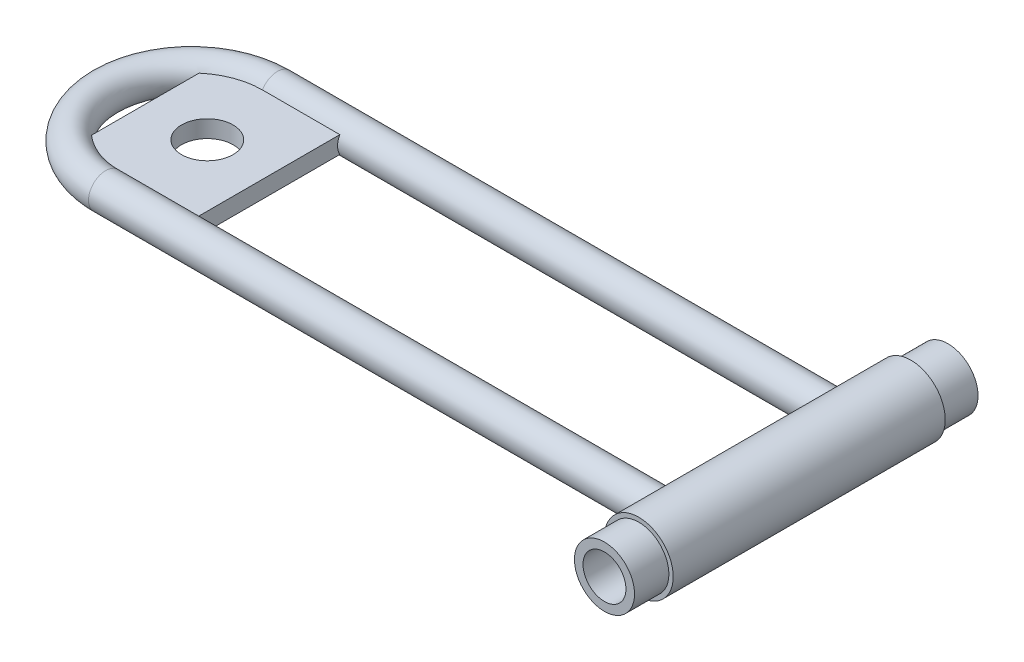
SolidWorks part; units mm, degrees
ref_plane "Front Plane" through (0, 0, 0) normal (0, 0, 1) x (1, 0, 0)
ref_plane "Top Plane" through (0, 0, 0) normal (0, 1, 0) x (1, 0, 0)
ref_plane "Right Plane" through (0, 0, 0) normal (1, 0, 0) x (0, 0, -1)
sketch "Sketch1" plane through (0, 0, 0) normal (0, 0, 1) x (1, 0, 0)
  circle A0 centre (0, 0) radius 6.35
  circle A1 centre (0, 0) radius 3.175
  dimension "D1" = 12.7
  dimension "D2" = 3.175
extrude "Boss-Extrude1" add sketch "Sketch1" along normal blind 62.992
ref_plane "Plane1" through (-3.81, 0, 0) normal (-1, 0, 0) x (0, 0, 1)
sketch "Sketch3" plane through (-3.81, 0, 0) normal (-1, 0, 0) x (0, 0, 1)
  line L0 (0, 0) -> (62.992, 0)
  line L1 (62.992, -6.35) -> (62.992, 6.35) construction
  circle A0 centre (-15.748, 0) radius 3.175
  circle A1 centre (47.244, 0) radius 3.175
  dimension "D3" = 6.35
  dimension "D4" = 6.35
  dimension "D1" = 15.748
  dimension "D2" = 15.748
sketch "Sketch4" plane through (0, 0, 0) normal (0, 1, 0) x (1, 0, 0)
  line L0 (-3.81, -15.6639) -> (-107.95, -15.6639)
  line L1 (-3.81, 0) -> (-3.81, -62.992) construction
  line L2 (-3.81, -47.0944) -> (-107.95, -47.0944)
  line L3 (-6.35, 0) -> (-6.35, -62.992) construction
  arc A0 (-107.95, -15.6639) -> (-107.95, -47.0944) centre (-107.95, -31.3792) ccw
  dimension "D1" = 101.6
  dimension "D2" = 15.7152
  dimension "D3" = 31.3792
sweep "Sweep1" add profiles "Sketch3" path "Sketch4"
ref_plane "Plane2" through (0, 0, 15.24) normal (0, 0, 1) x (1, 0, 0)
sketch "Sketch6" plane through (0, 0, 15.24) normal (0, 0, 1) x (1, 0, 0)
  line L0 (-116.5013, 0) -> (-93.6413, 0)
  line L3 (-93.6413, 0) -> (-116.5013, 0)
  line L4 (-93.6413, 0) -> (-93.6413, -1.5875)
  line L5 (-93.6413, -1.5875) -> (-116.5013, -1.5875)
  line L6 (-116.5013, 0) -> (-116.5013, -1.5875)
  line L7 (-93.6413, 0) -> (-116.5013, 0)
  line L8 (-93.6413, 0) -> (-93.6413, 1.5875)
  line L9 (-93.6413, 1.5875) -> (-116.5013, 1.5875)
  line L10 (-116.5013, 0) -> (-116.5013, 1.5875)
  circle A0 centre (0, 0) radius 3.175 construction
  point P3 (-105.0713, 0)
  dimension "D4" = 93.6413
  dimension "D1" = 22.86
  dimension "D2" = 1.5875
  dimension "D3" = 1.5875
extrude "Boss-Extrude3" add sketch "Sketch6" along normal blind 29.21 contours L0 L6 L5 L4 | L10 L0 L8 L9 region at (-105.0713, 0.7937, 15.24) region at (-105.0713, -0.7937, 15.24)
sketch "Sketch7" plane through (0, 1.5875, 0) normal (0, 1, 0) x (1, 0, 0)
  line L1 (-93.6413, -44.45) -> (-93.6413, -18.2639) construction
  circle A0 centre (-105.0713, -31.3411) radius 4.7625
  dimension "D3" = 9.525
  dimension "D1" = 11.43
  dimension "D2" = 9.906
extrude "Cut-Extrude1" cut sketch "Sketch7" against normal blind 29.21
sketch "Sketch9" plane through (0, 0, 0) normal (0, 0, -1) x (-1, 0, 0)
  circle A0 centre (0, 0) radius 6.35
  circle A1 centre (0, 0) radius 3.175
  circle A2 centre (0, 0) radius 6.35 construction
  dimension "D1" = 6.35
  dimension "D2" = 12.7
ref_plane "Plane3" through (0, 0, 31.496) normal (0, 0, 1) x (1, 0, 0)
extrude "Boss-Extrude5" add sketch "Sketch9" along normal blind 6.35
mirror "Mirror1" about plane through (0, 0, 31.496) normal (0, 0, 1) of "Boss-Extrude5"
sketch "Sketch10" plane through (0, 0, 69.342) normal (0, 0, 1) x (1, 0, 0)
  circle A0 centre (0, 0) radius 5.5562
  circle A1 centre (0, 0) radius 6.35
  dimension "D1" = 11.1125
  dimension "D2" = 12.7
extrude "Cut-Extrude6" cut sketch "Sketch10" against normal blind 12.7
sketch "Sketch12" plane through (0, 0, -6.35) normal (0, 0, -1) x (-1, 0, 0)
  circle A0 centre (0, 0) radius 5.5562
  circle A1 centre (0, 0) radius 6.35
  circle A2 centre (0, 0) radius 6.35 construction
  dimension "D1" = 11.1125
  dimension "D2" = 12.7
extrude "Cut-Extrude7" cut sketch "Sketch12" against normal blind 12.7
sketch "Sketch13" plane through (0, 0, 69.342) normal (0, 0, 1) x (1, 0, 0)
  circle A0 centre (0, 0) radius 5.5563
  circle A1 centre (0, 0) radius 3.175
  circle A2 centre (0, 0) radius 3.175 construction
  dimension "D1" = 6.35
  dimension "D2" = 11.1125
extrude "Cut-Extrude8" cut sketch "Sketch13" against normal blind 6.35
sketch "Sketch14" plane through (0, 0, -6.35) normal (0, 0, -1) x (-1, 0, 0)
  circle A0 centre (0, 0) radius 5.5563
  circle A1 centre (0, 0) radius 3.175
  circle A2 centre (0, 0) radius 3.175 construction
  dimension "D1" = 6.35
  dimension "D2" = 11.1125
extrude "Cut-Extrude9" cut sketch "Sketch14" against normal blind 6.35
sketch "Sketch16" plane through (0, 0, 0) normal (0, 0, -1) x (-1, 0, 0)
  circle A0 centre (0, 0) radius 3.9688
  dimension "D1" = 7.9375
extrude "Cut-Extrude11" cut sketch "Sketch16" against normal through all
sketch "Sketch18" plane through (0, 0, 0) normal (0, 0, -1) x (-1, 0, 0)
  circle A0 centre (0, 0) radius 5.5563
  circle A1 centre (0, 0) radius 3.9688
  circle A2 centre (0, 0) radius 3.9688 construction
  dimension "D1" = 7.9375
  dimension "D2" = 11.1125
extrude "Boss-Extrude7" add sketch "Sketch18" along normal blind 0.508
